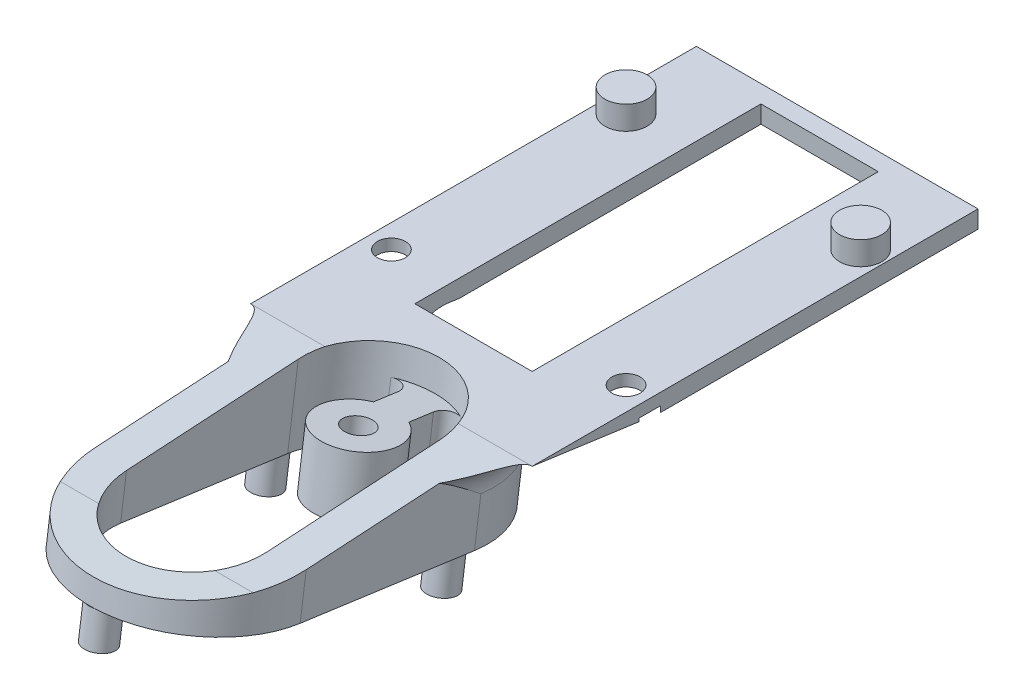
SolidWorks part; units mm, degrees
material "ABS"
ref_plane "Plan de face" through (0, 0, 0) normal (0, 0, 1) x (1, 0, 0)
ref_plane "Plan de dessus" through (0, 0, 0) normal (0, 1, 0) x (1, 0, 0)
ref_plane "Plan de droite" through (0, 0, 0) normal (1, 0, 0) x (0, 0, -1)
sketch "Esquisse1" plane through (0, 0, 0) normal (0, 1, 0) x (1, 0, 0)
  line L1 (-12, -19) -> (12, -19)
  line L2 (-12, -19) -> (-12, 19)
  line L3 (-12, 19) -> (12, 19)
  line L4 (12, -19) -> (12, 19)
  line L5 (-12, -19) -> (12, 19) construction
  line L6 (-12, 19) -> (12, -19) construction
  line L11 (-5, -12) -> (5, -12)
  line L12 (0, 2.75) -> (0, 0) construction
  line L13 (-5, -12) -> (-5, 17.5)
  line L14 (-5, 17.5) -> (5, 17.5)
  line L15 (5, -12) -> (5, 17.5)
  line L16 (-5, -12) -> (5, 17.5) construction
  line L17 (-5, 17.5) -> (5, -12) construction
  point P0 (0, 0)
  dimension "D1" = 24
  dimension "D2" = 38
  dimension "D3" = 1.5
  dimension "D4" = 7
  dimension "D5" = 7
extrude "Shape" add sketch "Esquisse1" along normal blind 1.5
sketch "Esquisse2" plane through (0, 1.5, 0) normal (0, 1, 0) x (1, 0, 0)
  line L0 (10, 19) -> (10, -19) construction
  line L1 (12, 19) -> (-12, 19) construction
  line L2 (-12, -19) -> (12, -19) construction
  line L3 (10, -19) -> (0, -19) construction
  circle A0 centre (10, -9) radius 1.2
  dimension "D2" = 2.4
  dimension "D1" = 10
  dimension "D3" = 10
extrude "VisHoles" cut sketch "Esquisse2" against normal blind 1.5
sketch "Esquisse3" plane through (0, 1.5, 0) normal (0, 1, 0) x (1, 0, 0)
  line L0 (12, 21) -> (-12, 21) construction
  line L1 (12, -19) -> (12, 19) construction
  line L2 (-12, 19) -> (-12, -19) construction
  line L3 (-12, -19) -> (12, -19) construction
  line L4 (0, 21) -> (0, -19) construction
  line L5 (10, -9) -> (10, 1) construction
  line L6 (0, 1) -> (10, 1) construction
  line L7 (10, 1) -> (10, 21) construction
  circle A0 centre (10, 11) radius 1.8
  line M6 (12, -19) -> (12, 19)
  dimension "D2" = 3.6
  dimension "D1" = 40
extrude "Lockers" add sketch "Esquisse3" along normal blind 2 contours A0 M6
sketch "Esquisse4" plane through (0, 0, 0) normal (0, 1, 0) x (1, 0, 0)
  circle A0 centre (10, -9) radius 2.2
  dimension "D1" = 4.4
extrude "ScrewHatRemover" cut sketch "Esquisse4" along normal blind 0.5
mirror "Symétrie1" about plane through (0, 0, 0) normal (1, 0, 0) of "ScrewHatRemover", "VisHoles", "Lockers"
sketch "Esquisse8" plane through (0, 0, 0) normal (1, 0, 0) x (0, 0, -1)
  line L0 (19, 1.5) -> (19, 3) construction
  line L1 (19, 0) -> (19, -0.7) construction
  line L2 (11, 3.5) -> (11, -9.7) construction
  line L3 (12.8, 3.5) -> (9.2, 3.5) construction
  line L4 (11, -9.7) -> (11, -20.2) construction
  line L5 (11, -14.95) -> (-61, -14.95) construction
  line L6 (-61, 0.3) -> (-61, -14.95) construction
  line L7 (-61, 0.3) -> (11, -9.7) construction
  line L8 (19, -0.7) -> (11, -0.7) construction
  line L9 (-19, 1.5) -> (-39, 0.2732)
  line L10 (-12.8864, -6.3824) -> (-12, 0)
  line L11 (-19, 0) -> (-9.9165, 0) construction
  line L12 (-39, 0.2732) -> (-47.3473, -0.0818)
  line L13 (-47.3473, -0.0818) -> (-47.5537, -1.5675)
  line L14 (-47.5537, -1.5675) -> (-12.8864, -6.3824)
  line L15 (-12, 0) -> (-12, 1.5)
  line L16 (-19, 1.5) -> (19, 1.5) construction
  line L17 (-12, 1.5) -> (-19, 1.5)
  line L18 (-19, 1.5) -> (-19, 0) construction
  line L20 (-61, 1.8144) -> (-61, 0.3) construction
  line L22 (14.5, -20.2) -> (7.5, -20.2) construction
  line L23 (14.5, -20.2) -> (14.5, -9.7) construction
  line L24 (14.5, -9.7) -> (7.5, -9.7) construction
  line L25 (7.5, -20.2) -> (7.5, -9.7) construction
  line L26 (14.5, -20.2) -> (7.5, -9.7) construction
  line L27 (14.5, -9.7) -> (7.5, -20.2) construction
  dimension "D1" = 1.5
  dimension "D2" = 3.7
  dimension "D4" = 15.25
  dimension "D5" = 10.5
  dimension "D6" = 9
  dimension "D8" = 35
  dimension "D9" = 20
  dimension "D10" = 7
  dimension "D12" = 7
  dimension "D7" = 1.5
  dimension "D3" = 72
extrude "Support" add sketch "Esquisse8" along normal up to surface and the other way up to surface up to face at (12, 0.5, 4.5) other way up to face at (-12, 0.5, 4.5)
sketch "Esquisse9" plane through (0, -8.0176, 1.1136) normal (0, -0.9905, 0.1376) x (1, 0, 0)
  line L0 (0, 46.8859) -> (0, -20.3316) construction
  line L1 (12, 46.8859) -> (-12, 46.8859) construction
  line L2 (0, 19.9944) -> (0, 34.9944) construction
  line L3 (-9, 19.9944) -> (-9, 34.9944)
  line L4 (9, 19.9944) -> (9, 34.9944)
  line L7 (-18.9339, 47.9078) -> (18.9339, 47.9078)
  line L8 (-18.9339, 47.9078) -> (-18.9339, 7.0811)
  line L9 (-18.9339, 7.0811) -> (18.9339, 7.0811)
  line L10 (18.9339, 47.9078) -> (18.9339, 7.0811)
  line L11 (-18.9339, 47.9078) -> (18.9339, 7.0811) construction
  line L12 (-18.9339, 7.0811) -> (18.9339, 47.9078) construction
  arc A0 (-9, 19.9944) -> (9, 19.9944) centre (0, 19.9944) ccw
  arc A1 (9, 34.9944) -> (-9, 34.9944) centre (0, 34.9944) ccw
  point P7 (0, 27.4944)
  point P19 (0, 27.4944)
  dimension "D2" = 15
  dimension "D1" = 18
extrude "Shaper Round" cut sketch "Esquisse9" against normal up to vertex (1.7342 mm away)
sketch "Esquisse10" plane through (0, 1.5, 0) normal (0, 1, 0) x (1, 0, 0)
  line L0 (0, 19) -> (0, -44.6897) construction
  line L1 (12, 19) -> (-12, 19) construction
  line L2 (0, -35.4348) -> (0, -20.9179) construction
  line L3 (-6, -35.4348) -> (-6, -20.9179)
  line L4 (6, -35.4348) -> (6, -20.9179)
  line L5 (9, -20.9179) -> (9, -35.7752) construction
  line L6 (9, -19.9864) -> (9, -35.2605) construction
  line L8 (-9, -20.9179) -> (0, -20.9179) construction
  line L9 (9, -35.4348) -> (-9.133, -35.4348) construction
  arc A0 (-6, -35.4348) -> (6, -35.4348) centre (0, -35.4348) ccw
  arc A1 (6, -20.9179) -> (-6, -20.9179) centre (0, -20.9179) ccw
  ellipse E0 centre (0, -35.7752) end of major axis (-9, -35.7752) minor radius 8.9144 (-9, -35.7752) -> (9, -35.7752) ccw construction
  point P14 (0, -28.1763)
  dimension "D1" = 3
extrude "Hole Middle" cut sketch "Esquisse10" along direction (0, -0.9905, 0.1376) on the side against the normal through all
sketch "Esquisse13" plane through (0, -8.0176, 1.1136) normal (0, -0.9905, 0.1376) x (1, 0, 0)
  line L0 (0, 0) -> (0, 18.3979) construction
  line L1 (1.5, 18.7713) -> (1.5, 12.0923)
  line L2 (1.5, 12.0923) -> (0, 12.0923)
  line L3 (-1.5, 12.0923) -> (-1.5, 18.7713)
  line L4 (-1.5, 12.0923) -> (0, 12.0923)
  line L5 (-5, 12.0923) -> (5, 12.0923) construction
  circle A0 centre (0, 21.5979) radius 3.2
  circle A1 centre (0, 21.5979) radius 1.2
  dimension "D1" = 2.4
  dimension "D3" = 1.5
extrude "VisFixation" add sketch "Esquisse13" against normal blind 5
fillet "Congé1" radius 1 2 edges
sketch "Profile" plane through (0, -8.0176, 1.1136) normal (0, -0.9905, 0.1376) x (1, 0, 0)
  line L0 (6, 20.9253) -> (-6, 20.9253) construction
  line L1 (6, 35.3043) -> (-6, 35.3043) construction
  line L2 (0, 20.9253) -> (0, 35.3043) construction
  line L3 (-7.4973, 20.9253) -> (-7.4973, 35.3043) construction
  line L4 (7.4973, 20.9253) -> (7.4973, 35.3043) construction
  line L7 (-6, 35.3043) -> (-7.4973, 35.3043) construction
  line L8 (-7.4973, 35.3043) -> (-8.9947, 35.3043) construction
  line L10 (0, 35.3043) -> (0, 42.8016) construction
  arc A0 (-7.4973, 20.9253) -> (7.4973, 20.9253) centre (0, 20.9253) ccw construction
  arc A1 (7.4973, 35.3043) -> (-7.4973, 35.3043) centre (0, 35.3043) ccw construction
  arc A3 (9, 34.9944) -> (-9, 34.9944) centre (0, 34.9944) ccw construction
  point P10 (0, 28.1148)
sketch "Esquisse15" plane through (0, -8.0176, 1.1136) normal (0, -0.9905, 0.1376) x (1, 0, 0)
  circle A0 centre (0, 42.8016) radius 1.25
  arc A1 (7.4973, 35.3043) -> (-7.4973, 35.3043) centre (0, 35.3043) ccw construction
  circle A2 centre (-7.4973, 20.9253) radius 1.25
  circle A3 centre (7.4973, 20.9253) radius 1.25
  dimension "D1" = 2.5
extrude "Plots" add sketch "Esquisse15" along normal blind 3
sketch "Mesures" plane through (0, 0, 0) normal (1, 0, 0) x (0, 0, -1)
  line L0 (-43.9209, -5.1009) -> (19.1793, -13.8648) construction
  line L1 (-45.159, -4.9289) -> (-42.6828, -5.2729) construction
  line L2 (11, 3.5) -> (11, -17.3006) construction
  line L3 (12.8, 3.5) -> (9.2, 3.5) construction
  line L4 (-21.8183, -0.0939) -> (-22.9188, -8.0178) construction
  line L5 (-20.6297, -0.259) -> (-23.0069, 0.0712) construction
  point P8 (11, -12.7288)
  dimension "D1" = 34.2444
fillet "Congé2" radius 3 2 edges at (-7.3986, 0.9283, 14.8837) (7.3986, 0.9283, 14.8837)
equation "\"entretoiseBearing\"= 1.5mm"
equation "\"length_tibia\"= 206mm"
equation "\"length_femur\"= 117mm"
equation "\"length_coxa\"= 27mm"
equation "\"height\"= 40mm"
equation "\"width\"= 100mm"
equation "\"lever\"= 40mm"
equation "\"errorFlat\"= 0.20mm"
equation "\"errorFlat_tight\"= 0.15mm"
equation "\"errorCircle\"= 0.40mm"
equation "\"errorCircle_tight\" = 0.30mm"
equation "\"cuticule\"=1.5mm"
equation "\"cuticule_attach_w\"=10mm"
equation "\"cuticule_attach_h\"=2.5mm"
equation "\"depthMagnet\"= 1mm"
equation "\"insert_d\" = 3.2mm"
equation "\"insert_l\" = 5mm"
equation "\"D2@Esquisse2\"= 2.00mm + \"errorCircle\""
equation "\"D2@Esquisse3\"= 4 - \"errorCircle\""
equation "\"D1@Esquisse4\"=4 + \"errorCircle\""
equation "\"D2@Esquisse8\"= 3.5 + \"errorFlat\""
equation "\"D1@Esquisse13\"= 2 + \"errorCircle\""
equation "\"D7@Esquisse8\"= 1.5"
